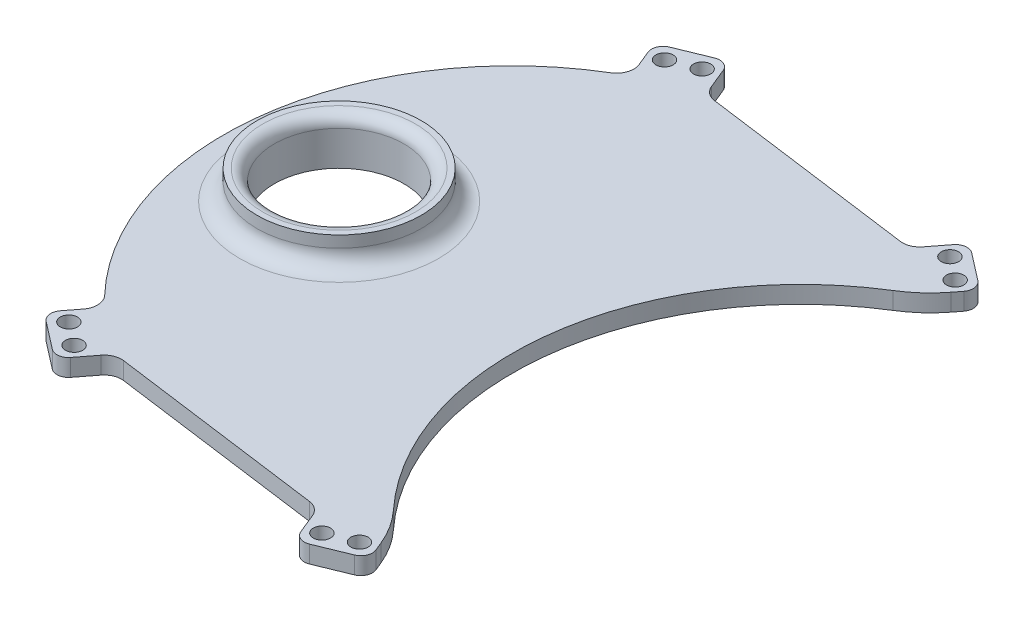
SolidWorks part; units mm, degrees
ref_plane "Front" through (0, 0, 0) normal (0, 0, 1) x (1, 0, 0)
ref_plane "Top" through (0, 0, 0) normal (0, 1, 0) x (1, 0, 0)
ref_plane "Right" through (0, 0, 0) normal (1, 0, 0) x (0, 0, -1)
sketch "Sketch1" plane through (0, 0, 0) normal (0, 1, 0) x (1, 0, 0)
  line L0 (-34.3716, -36.3125) -> (-38.9568, -42.2476)
  line L1 (-38.9568, -42.2476) -> (-31.0432, -48.3612)
  line L2 (-31.0432, -48.3612) -> (-26.458, -42.4261)
  line L3 (14.2617, -47.9229) -> (17.1091, -54.8614)
  line L4 (17.1091, -54.8614) -> (26.3604, -51.0648)
  line L5 (26.3604, -51.0648) -> (23.513, -44.1264)
  line L6 (34.3716, 36.3125) -> (38.9568, 42.2476)
  line L7 (38.9568, 42.2476) -> (31.0432, 48.3612)
  line L8 (31.0432, 48.3612) -> (26.458, 42.4261)
  line L9 (-14.2617, 47.9229) -> (-17.1091, 54.8614)
  line L10 (-17.1091, 54.8614) -> (-26.3604, 51.0648)
  line L11 (-26.3604, 51.0648) -> (-23.513, 44.1264)
  circle A0 centre (0, 0) radius 50 construction
  arc A1 (-34.3716, -36.3125) -> (-26.458, -42.4261) centre (0, 0) ccw
  arc A2 (14.2617, -47.9229) -> (23.513, -44.1264) centre (0, 0) ccw
  arc A3 (34.3716, 36.3125) -> (26.458, 42.4261) centre (0, 0) ccw
  arc A4 (-14.2617, 47.9229) -> (-23.513, 44.1264) centre (0, 0) ccw
  point P5 (-35, -45.3044)
  point P15 (0, 0)
  point P20 (0, 0)
  point P25 (0, 0)
  dimension "D1" = 100
  dimension "D2" = 7.5
  dimension "D3" = 10
  dimension "D4" = 35
  dimension "D6" = 60
  dimension "D8" = 180
  dimension "D10" = 120
  dimension "D5" = 2
  dimension "D7" = 2
  dimension "D9" = 2
extrude "Boss-Extrude1" add sketch "Sketch1" along normal blind 3
sketch "Sketch2" plane through (0, 3, 0) normal (0, 1, 0) x (1, 0, 0)
  line L2 (-26.458, -42.4261) -> (14.2617, -47.9229)
  line L4 (26.458, 42.4261) -> (-14.2617, 47.9229)
  arc A0 (-23.513, 44.1264) -> (-34.3716, -36.3125) centre (0, 0) ccw
  arc A1 (34.3716, 36.3125) -> (23.513, -44.1264) centre (57.8846, -7.8139) ccw
  arc A2 (14.2617, -47.9229) -> (23.513, -44.1264) centre (0, 0) ccw
  arc A3 (14.2617, -47.9229) -> (23.513, -44.1264) centre (0, 0) ccw
  arc A5 (-34.3716, -36.3125) -> (-26.458, -42.4261) centre (0, 0) ccw
  arc A6 (-34.3716, -36.3125) -> (-26.458, -42.4261) centre (0, 0) ccw
  arc A8 (-14.2617, 47.9229) -> (-23.513, 44.1264) centre (0, 0) ccw
  arc A9 (-14.2617, 47.9229) -> (-23.513, 44.1264) centre (0, 0) ccw
  circle A10 centre (-30, 0) radius 11.25
  arc A11 (34.3716, 36.3125) -> (26.458, 42.4261) centre (0, 0) ccw
  arc A12 (34.3716, 36.3125) -> (26.458, 42.4261) centre (0, 0) ccw
  dimension "D5" = 22.5
  dimension "D7" = 50
  dimension "D8" = 50
  dimension "D6" = 30
  dimension "D1" = 0
  dimension "D2" = 0
  dimension "D3" = 0
  dimension "D4" = 0
extrude "Boss-Extrude2" add sketch "Sketch2" against normal up to surface (3 mm away) up to face at (-32.7457, 0, 42.3864)
sketch "Sketch3" plane through (0, 3, 0) normal (0, 1, 0) x (1, 0, 0)
  line L0 (-33.3188, -43.1282) -> (-37.2755, -40.0714) construction
  line L1 (-31.0432, -48.3612) -> (-26.458, -42.4261) construction
  line L2 (-34.3716, -36.3125) -> (-38.9568, -42.2476) construction
  line L3 (-35, -45.3044) -> (-33.3188, -43.1282) construction
  line L4 (-38.9568, -42.2476) -> (-31.0432, -48.3612) construction
  circle A0 centre (-35.2971, -41.5998) radius 1.5
  circle A1 centre (-31.3404, -44.6566) radius 1.5
  point P12 (-35.2971, -41.5998)
  dimension "D1" = 3
  dimension "D2" = 2.75
extrude "Cut-Extrude1" cut sketch "Sketch3" against normal up to next
fillet "Fillet1" radius 2 2 edges at (-31.0432, 1.5, 48.3612) (-38.9568, 1.5, 42.2476)
sketch "Sketch4" plane through (0, 3, 0) normal (0, 1, 0) x (1, 0, 0)
  circle A1 centre (-30, 0) radius 14.25
  circle A2 centre (-30, 0) radius 11.25
  circle A3 centre (-30, 0) radius 11.25
  dimension "D1" = 0
  dimension "D2" = 3
extrude "Boss-Extrude3" add sketch "Sketch4" along normal blind 5
fillet "Fillet3" radius 2 1 edges at (-30, 8, 11.25)
fillet "Fillet2" radius 3 1 edges at (-30, 3, 14.25)
sketch "Sketch6" plane through (0, 3, 0) normal (0, 1, 0) x (1, 0, 0)
  line L0 (16.0651, -52.3172) -> (20.6907, -50.419) construction
  line L1 (14.2617, -47.9229) -> (17.1091, -54.8614) construction
  line L2 (20.6907, -50.419) -> (21.7348, -52.9631) construction
  line L3 (17.1091, -54.8614) -> (26.3604, -51.0648) construction
  line L4 (26.3604, -51.0648) -> (23.513, -44.1264) construction
  circle A0 centre (18.3779, -51.3681) radius 1.5
  circle A1 centre (23.0036, -49.4699) radius 1.5
  point P8 (18.3779, -51.3681)
  dimension "D2" = 3
  dimension "D1" = 2.75
extrude "Cut-Extrude2" cut sketch "Sketch6" against normal up to next
fillet "Fillet4" radius 2 2 edges at (26.3604, 1.5, 51.0648) (17.1091, 1.5, 54.8614)
sketch "Sketch7" plane through (0, 3, 0) normal (0, 1, 0) x (1, 0, 0)
  line L0 (-16.0651, 52.3172) -> (-20.6907, 50.419) construction
  line L1 (-14.2617, 47.9229) -> (-17.1091, 54.8614) construction
  line L2 (-20.6907, 50.419) -> (-21.7348, 52.9631) construction
  line L3 (-17.1091, 54.8614) -> (-26.3604, 51.0648) construction
  line L4 (-26.3604, 51.0648) -> (-23.513, 44.1264) construction
  circle A0 centre (-18.3779, 51.3681) radius 1.5
  circle A1 centre (-23.0036, 49.4699) radius 1.5
  point P13 (-18.3779, 51.3681)
  dimension "D2" = 3
  dimension "D1" = 2.75
extrude "Cut-Extrude3" cut sketch "Sketch7" against normal up to next
fillet "Fillet5" radius 2 2 edges at (-26.3604, 1.5, -51.0648) (-17.1091, 1.5, -54.8614)
sketch "Sketch8" plane through (0, 3, 0) normal (0, 1, 0) x (1, 0, 0)
  line L0 (37.2755, 40.0714) -> (33.3188, 43.1282) construction
  line L1 (34.3716, 36.3125) -> (38.9568, 42.2476) construction
  line L2 (33.3188, 43.1282) -> (35, 45.3044) construction
  line L3 (38.9568, 42.2476) -> (31.0432, 48.3612) construction
  circle A0 centre (35.2971, 41.5998) radius 1.5
  circle A1 centre (31.3404, 44.6566) radius 1.5
  point P10 (35.2971, 41.5998)
  dimension "D2" = 3
  dimension "D1" = 2.75
extrude "Cut-Extrude4" cut sketch "Sketch8" against normal up to next
fillet "Fillet6" radius 2 2 edges at (38.9568, 1.5, -42.2476) (31.0432, 1.5, -48.3612)
fillet "Fillet7" radius 3 6 edges at (-23.513, 1.5, -44.1264) (-14.2617, 1.5, -47.9229) (26.458, 1.5, -42.4261) (14.2617, 1.5, 47.9229) (-26.458, 1.5, 42.4261) (-34.3716, 1.5, 36.3125)
fillet "Fillet8" radius 20 2 edges at (34.3716, 1.5, -36.3125) (23.513, 1.5, 44.1264)
